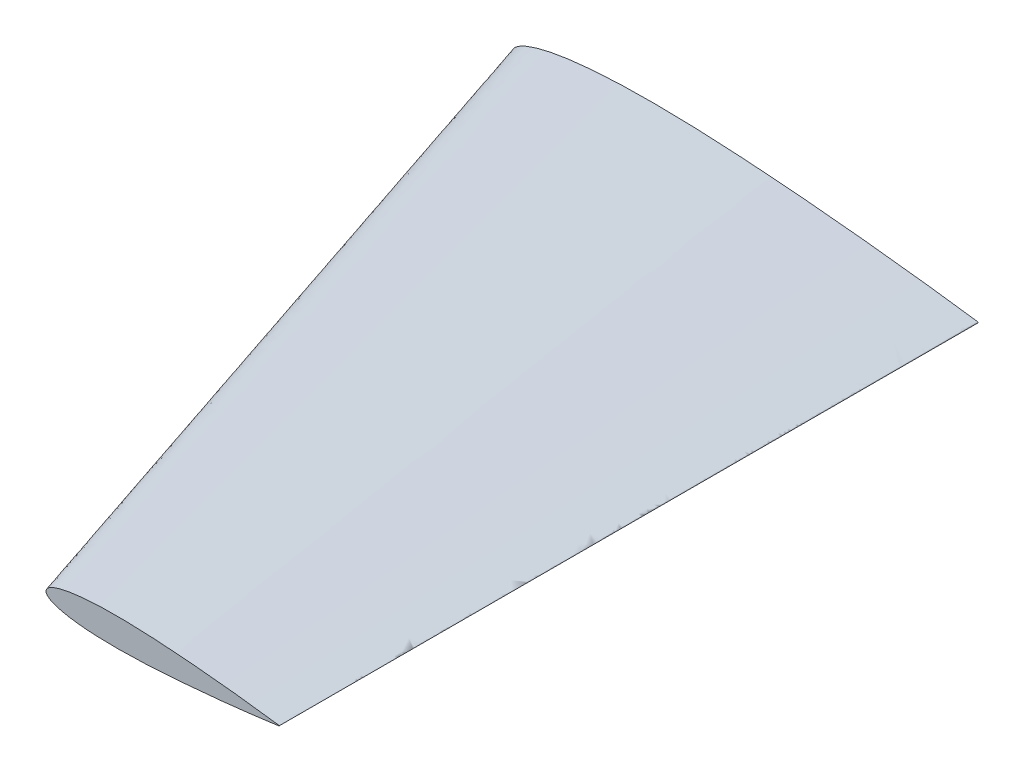
SolidWorks part; units mm, degrees
ref_plane "Front Plane" through (0, 0, 0) normal (1, 0, 0) x (0, 1, 0)
ref_plane "Top Plane" through (0, 0, 0) normal (0, 0, 1) x (0, 1, 0)
ref_plane "Right Plane" through (0, 0, 0) normal (0, 1, 0) x (-1, 0, 0)
curve "Curve2"
  spline degree 3 poles (90, 0.1134, 0) (89.9538, 0.1199, 0) (89.7691, 0.1458, 0) (89.3547, 0.2036, 0) (88.6668, 0.299, 0) (87.7097, 0.43, 0) (86.4894, 0.595, 0) (85.0132, 0.7907, 0) (83.2903, 1.0144, 0) (81.3314, 1.2627, 0) (79.1484, 1.5322, 0) (76.7549, 1.8188, 0) (74.1657, 2.1193, 0) (71.3966, 2.4294, 0) (68.4648, 2.7453, 0) (65.3883, 3.0632, 0) (62.1861, 3.379, 0) (58.878, 3.6881, 0) (55.4843, 3.9866, 0) (52.026, 4.2695, 0) (48.5244, 4.5321, 0) (45.001, 4.7696, 0) (41.4775, 4.977, 0) (37.9757, 5.149, 0) (34.5172, 5.2811, 0) (31.1233, 5.369, 0) (27.8148, 5.4084, 0) (24.6121, 5.3961, 0) (21.5349, 5.3298, 0) (18.6023, 5.2078, 0) (15.8322, 5.0298, 0) (13.2417, 4.7963, 0) (10.8466, 4.5092, 0) (8.6616, 4.1708, 0) (6.6998, 3.7847, 0) (4.9728, 3.3553, 0) (3.4903, 2.8868, 0) (2.26, 2.3835, 0) (1.2857, 1.8489, 0) (0.569, 1.2818, 0) (0.1099, 0.6686, 0) (-0.0512, 0, 0) (0.1099, -0.6686, 0) (0.569, -1.2818, 0) (1.2857, -1.8489, 0) (2.26, -2.3835, 0) (3.4903, -2.8868, 0) (4.9728, -3.3553, 0) (6.6998, -3.7847, 0) (8.6616, -4.1708, 0) (10.8466, -4.5092, 0) (13.2417, -4.7963, 0) (15.8322, -5.0298, 0) (18.6023, -5.2078, 0) (21.5349, -5.3298, 0) (24.6121, -5.3961, 0) (27.8148, -5.4084, 0) (31.1233, -5.369, 0) (34.5172, -5.2811, 0) (37.9757, -5.149, 0) (41.4775, -4.977, 0) (45.001, -4.7696, 0) (48.5244, -4.5321, 0) (52.026, -4.2695, 0) (55.4843, -3.9866, 0) (58.878, -3.6881, 0) (62.1861, -3.379, 0) (65.3883, -3.0632, 0) (68.4648, -2.7453, 0) (71.3966, -2.4294, 0) (74.1657, -2.1193, 0) (76.7549, -1.8188, 0) (79.1484, -1.5322, 0) (81.3314, -1.2627, 0) (83.2903, -1.0144, 0) (85.0132, -0.7907, 0) (86.4894, -0.595, 0) (87.7097, -0.43, 0) (88.6668, -0.299, 0) (89.3547, -0.2036, 0) (89.7691, -0.1458, 0) (89.9538, -0.1199, 0) (90, -0.1134, 0) knots 0 0 0 0 0.000763 0.003048 0.006841 0.012116 0.018841 0.026973 0.03646 0.047243 0.059254 0.072417 0.086651 0.101866 0.117969 0.134858 0.152428 0.170572 0.189175 0.208122 0.227297 0.24658 0.265853 0.284997 0.303895 0.322433 0.340499 0.357984 0.374788 0.390812 0.405965 0.420162 0.433328 0.445394 0.456301 0.466004 0.474472 0.481696 0.487704 0.492583 0.496544 0.5 0.503456 0.507417 0.512296 0.518304 0.525528 0.533996 0.543699 0.554606 0.566672 0.579838 0.594035 0.609188 0.625212 0.642016 0.659501 0.677567 0.696105 0.715003 0.734147 0.75342 0.772703 0.791878 0.810825 0.829428 0.847572 0.865142 0.882031 0.898134 0.913349 0.927583 0.940746 0.952757 0.96354 0.973027 0.981159 0.987884 0.993159 0.996952 0.999237 1 1 1 1
sketch "Sketch2" plane through (0, 0, 0) normal (0, 0, 1) x (0, 1, 0)
  arc A0 (-0.1134, -90) -> (0.1134, -90) centre (0, -89.9841) ccw
  spline S0 degree 3 poles (1966.8421, -449.5678) (-10.9329, -144.6657) (-3.7009, -117.3601) (0.2036, -89.3547) (0.299, -88.6668) (0.43, -87.7097) (0.595, -86.4894) (0.7907, -85.0132) (1.0144, -83.2903) (1.2627, -81.3314) (1.5322, -79.1484) (1.8188, -76.7549) (2.1193, -74.1657) (2.4294, -71.3966) (2.7453, -68.4648) (3.0632, -65.3883) (3.379, -62.1861) (3.6881, -58.878) (3.9866, -55.4843) (4.2695, -52.026) (4.5321, -48.5244) (4.7696, -45.001) (4.977, -41.4775) (5.149, -37.9757) (5.2811, -34.5172) (5.369, -31.1233) (5.4084, -27.8148) (5.3961, -24.6121) (5.3298, -21.5349) (5.2078, -18.6023) (5.0298, -15.8322) (4.7963, -13.2417) (4.5092, -10.8466) (4.1708, -8.6616) (3.7847, -6.6998) (3.3553, -4.9728) (2.8868, -3.4903) (2.3835, -2.26) (1.8489, -1.2857) (1.2818, -0.569) (0.6686, -0.1099) (0, 0.0512) (-0.6686, -0.1099) (-1.2818, -0.569) (-1.8489, -1.2857) (-2.3835, -2.26) (-2.8868, -3.4903) (-3.3553, -4.9728) (-3.7847, -6.6998) (-4.1708, -8.6616) (-4.5092, -10.8466) (-4.7963, -13.2417) (-5.0298, -15.8322) (-5.2078, -18.6023) (-5.3298, -21.5349) (-5.3961, -24.6121) (-5.4084, -27.8148) (-5.369, -31.1233) (-5.2811, -34.5172) (-5.149, -37.9757) (-4.977, -41.4775) (-4.7696, -45.001) (-4.5321, -48.5244) (-4.2695, -52.026) (-3.9866, -55.4843) (-3.6881, -58.878) (-3.379, -62.1861) (-3.0632, -65.3883) (-2.7453, -68.4648) (-2.4294, -71.3966) (-2.1193, -74.1657) (-1.8188, -76.7549) (-1.5322, -79.1484) (-1.2627, -81.3314) (-1.0144, -83.2903) (-0.7907, -85.0132) (-0.595, -86.4894) (-0.43, -87.7097) (-0.299, -88.6668) (-0.2036, -89.3547) (3.7009, -117.36) (10.9329, -144.6654) (-1966.8144, -449.5636) knots -0.45542 -0.45542 -0.45542 -0.45542 0.000763 0.003048 0.006841 0.012116 0.018841 0.026973 0.03646 0.047243 0.059254 0.072417 0.086651 0.101866 0.117969 0.134858 0.152428 0.170572 0.189175 0.208122 0.227297 0.24658 0.265853 0.284997 0.303895 0.322433 0.340499 0.357984 0.374788 0.390812 0.405965 0.420162 0.433328 0.445394 0.456301 0.466004 0.474472 0.481696 0.487704 0.492583 0.496544 0.5 0.503456 0.507417 0.512296 0.518304 0.525528 0.533996 0.543699 0.554606 0.566672 0.579838 0.594035 0.609188 0.625212 0.642016 0.659501 0.677567 0.696105 0.715003 0.734147 0.75342 0.772703 0.791878 0.810825 0.829428 0.847572 0.865142 0.882031 0.898134 0.913349 0.927583 0.940746 0.952757 0.96354 0.973027 0.981159 0.987884 0.993159 0.996952 0.999237 1.455418 1.455418 1.455418 1.455418 only from (0.1134, -90) to (-0.1134, -90) construction
  spline S1 degree 3 poles (0.1134, -90) (0.1199, -89.9538) (0.1458, -89.7691) (0.2036, -89.3547) (0.299, -88.6668) (0.43, -87.7097) (0.595, -86.4894) (0.7907, -85.0132) (1.0144, -83.2903) (1.2627, -81.3314) (1.5322, -79.1484) (1.8188, -76.7549) (2.1193, -74.1657) (2.4294, -71.3966) (2.7453, -68.4648) (3.0632, -65.3883) (3.379, -62.1861) (3.6881, -58.878) (3.9866, -55.4843) (4.2695, -52.026) (4.5321, -48.5244) (4.7696, -45.001) (4.977, -41.4775) (5.149, -37.9757) (5.2811, -34.5172) (5.369, -31.1233) (5.4084, -27.8148) (5.3961, -24.6121) (5.3298, -21.5349) (5.2078, -18.6023) (5.0298, -15.8322) (4.7963, -13.2417) (4.5092, -10.8466) (4.1708, -8.6616) (3.7847, -6.6998) (3.3553, -4.9728) (2.8868, -3.4903) (2.3835, -2.26) (1.8489, -1.2857) (1.2818, -0.569) (0.6686, -0.1099) (0, 0.0512) (-0.6686, -0.1099) (-1.2818, -0.569) (-1.8489, -1.2857) (-2.3835, -2.26) (-2.8868, -3.4903) (-3.3553, -4.9728) (-3.7847, -6.6998) (-4.1708, -8.6616) (-4.5092, -10.8466) (-4.7963, -13.2417) (-5.0298, -15.8322) (-5.2078, -18.6023) (-5.3298, -21.5349) (-5.3961, -24.6121) (-5.4084, -27.8148) (-5.369, -31.1233) (-5.2811, -34.5172) (-5.149, -37.9757) (-4.977, -41.4775) (-4.7696, -45.001) (-4.5321, -48.5244) (-4.2695, -52.026) (-3.9866, -55.4843) (-3.6881, -58.878) (-3.379, -62.1861) (-3.0632, -65.3883) (-2.7453, -68.4648) (-2.4294, -71.3966) (-2.1193, -74.1657) (-1.8188, -76.7549) (-1.5322, -79.1484) (-1.2627, -81.3314) (-1.0144, -83.2903) (-0.7907, -85.0132) (-0.595, -86.4894) (-0.43, -87.7097) (-0.299, -88.6668) (-0.2036, -89.3547) (-0.1458, -89.7691) (-0.1199, -89.9538) (-0.1134, -90) knots 0 0 0 0 0.000763 0.003048 0.006841 0.012116 0.018841 0.026973 0.03646 0.047243 0.059254 0.072417 0.086651 0.101866 0.117969 0.134858 0.152428 0.170572 0.189175 0.208122 0.227297 0.24658 0.265853 0.284997 0.303895 0.322433 0.340499 0.357984 0.374788 0.390812 0.405965 0.420162 0.433328 0.445394 0.456301 0.466004 0.474472 0.481696 0.487704 0.492583 0.496544 0.5 0.503456 0.507417 0.512296 0.518304 0.525528 0.533996 0.543699 0.554606 0.566672 0.579838 0.594035 0.609188 0.625212 0.642016 0.659501 0.677567 0.696105 0.715003 0.734147 0.75342 0.772703 0.791878 0.810825 0.829428 0.847572 0.865142 0.882031 0.898134 0.913349 0.927583 0.940746 0.952757 0.96354 0.973027 0.981159 0.987884 0.993159 0.996952 0.999237 1 1 1 1
curve "Curve3"
  spline degree 3 poles (45, 0.0567, 0) (44.9912, 0.0579, 0) (44.9562, 0.0628, 0) (44.8775, 0.0739, 0) (44.7466, 0.0922, 0) (44.5636, 0.1176, 0) (44.3292, 0.15, 0) (44.0438, 0.1892, 0) (43.708, 0.2349, 0) (43.3227, 0.2868, 0) (42.8888, 0.3447, 0) (42.4073, 0.4081, 0) (41.8793, 0.4768, 0) (41.306, 0.5503, 0) (40.6888, 0.6281, 0) (40.0291, 0.71, 0) (39.3285, 0.7954, 0) (38.5885, 0.884, 0) (37.811, 0.9753, 0) (36.9978, 1.0688, 0) (36.1506, 1.1641, 0) (35.2716, 1.2607, 0) (34.3628, 1.3582, 0) (33.4263, 1.4561, 0) (32.4642, 1.554, 0) (31.4789, 1.6513, 0) (30.4726, 1.7476, 0) (29.4476, 1.8424, 0) (28.4065, 1.935, 0) (27.3515, 2.0251, 0) (26.2853, 2.112, 0) (25.2101, 2.1952, 0) (24.1287, 2.2742, 0) (23.0434, 2.3482, 0) (21.9569, 2.4169, 0) (20.8717, 2.4795, 0) (19.7902, 2.5354, 0) (18.7151, 2.5842, 0) (17.6488, 2.6253, 0) (16.5938, 2.6582, 0) (15.5526, 2.6822, 0) (14.5276, 2.6971, 0) (13.5213, 2.7024, 0) (12.5359, 2.6978, 0) (11.5738, 2.6829, 0) (10.6371, 2.6576, 0) (9.7282, 2.6217, 0) (8.8491, 2.5751, 0) (8.0019, 2.5179, 0) (7.1884, 2.45, 0) (6.4108, 2.3718, 0) (5.6707, 2.2834, 0) (4.9698, 2.1851, 0) (4.3099, 2.0772, 0) (3.6923, 1.9603, 0) (3.1187, 1.8346, 0) (2.5902, 1.7008, 0) (2.108, 1.5593, 0) (1.6732, 1.4107, 0) (1.2869, 1.2554, 0) (0.9496, 1.0939, 0) (0.662, 0.9266, 0) (0.4245, 0.7537, 0) (0.2376, 0.5749, 0) (0.1017, 0.3898, 0) (0.0185, 0.1974, 0) (-0.009, 0, 0) (0.0185, -0.1974, 0) (0.1017, -0.3898, 0) (0.2376, -0.5749, 0) (0.4245, -0.7537, 0) (0.662, -0.9266, 0) (0.9496, -1.0939, 0) (1.2869, -1.2554, 0) (1.6732, -1.4107, 0) (2.108, -1.5593, 0) (2.5902, -1.7008, 0) (3.1187, -1.8346, 0) (3.6923, -1.9603, 0) (4.3099, -2.0772, 0) (4.9698, -2.1851, 0) (5.6707, -2.2834, 0) (6.4108, -2.3718, 0) (7.1884, -2.45, 0) (8.0019, -2.5179, 0) (8.8491, -2.5751, 0) (9.7282, -2.6217, 0) (10.6371, -2.6576, 0) (11.5738, -2.6829, 0) (12.5359, -2.6978, 0) (13.5213, -2.7024, 0) (14.5276, -2.6971, 0) (15.5526, -2.6822, 0) (16.5938, -2.6582, 0) (17.6488, -2.6253, 0) (18.7151, -2.5842, 0) (19.7902, -2.5354, 0) (20.8717, -2.4795, 0) (21.9569, -2.4169, 0) (23.0434, -2.3482, 0) (24.1287, -2.2742, 0) (25.2101, -2.1952, 0) (26.2853, -2.112, 0) (27.3515, -2.0251, 0) (28.4065, -1.935, 0) (29.4476, -1.8424, 0) (30.4726, -1.7476, 0) (31.4789, -1.6513, 0) (32.4642, -1.554, 0) (33.4263, -1.4561, 0) (34.3628, -1.3582, 0) (35.2716, -1.2607, 0) (36.1506, -1.1641, 0) (36.9978, -1.0688, 0) (37.811, -0.9753, 0) (38.5885, -0.884, 0) (39.3285, -0.7954, 0) (40.0291, -0.71, 0) (40.6888, -0.6281, 0) (41.306, -0.5503, 0) (41.8793, -0.4768, 0) (42.4073, -0.4081, 0) (42.8888, -0.3447, 0) (43.3227, -0.2868, 0) (43.708, -0.2349, 0) (44.0438, -0.1892, 0) (44.3292, -0.15, 0) (44.5636, -0.1176, 0) (44.7466, -0.0922, 0) (44.8775, -0.0739, 0) (44.9562, -0.0628, 0) (44.9912, -0.0579, 0) (45, -0.0567, 0) knots 0 0 0 0 0.000289 0.001156 0.002598 0.004612 0.007194 0.010336 0.014031 0.018271 0.023046 0.028343 0.03415 0.040454 0.047239 0.054489 0.062186 0.070314 0.078852 0.08778 0.097077 0.106722 0.116691 0.126961 0.137507 0.148306 0.159331 0.170557 0.181957 0.193504 0.205172 0.216932 0.228758 0.240621 0.252495 0.26435 0.276161 0.287898 0.299536 0.311047 0.322405 0.333584 0.344559 0.355306 0.3658 0.376018 0.385938 0.395538 0.404798 0.413699 0.422222 0.430349 0.438066 0.445357 0.452209 0.458611 0.464554 0.47003 0.475035 0.479569 0.483637 0.48725 0.490431 0.493219 0.495674 0.497891 0.5 0.502109 0.504326 0.506781 0.509569 0.51275 0.516363 0.520431 0.524965 0.52997 0.535446 0.541389 0.547791 0.554643 0.561934 0.569651 0.577778 0.586301 0.595202 0.604462 0.614062 0.623982 0.6342 0.644694 0.655441 0.666416 0.677595 0.688953 0.700464 0.712102 0.723839 0.73565 0.747505 0.759379 0.771242 0.783068 0.794828 0.806496 0.818043 0.829443 0.840669 0.851694 0.862493 0.873039 0.883309 0.893278 0.902923 0.91222 0.921148 0.929686 0.937814 0.945511 0.952761 0.959546 0.96585 0.971657 0.976954 0.981729 0.985969 0.989664 0.992806 0.995388 0.997402 0.998844 0.999711 1 1 1 1
ref_plane "Plane1" through (0, 0, 135) normal (0, 0, 1) x (0, 1, 0)
sketch "Sketch3" plane through (0, 0, 135) normal (0, 0, 1) x (0, 1, 0)
  arc A5 (-0.0567, -89.992) -> (0.0567, -89.992) centre (0, -89.9841) ccw
  spline S3 degree 3 poles (0.0567, -89.992) (0.0579, -89.9833) (0.0628, -89.9483) (0.0739, -89.8696) (0.1164, -89.5652) (0.1702, -89.1751) (0.2349, -88.7) (0.2868, -88.3148) (0.3447, -87.8809) (0.4081, -87.3993) (0.4768, -86.8713) (0.5503, -86.298) (0.6281, -85.6808) (0.71, -85.0211) (0.8601, -83.7902) (1.0118, -82.4964) (1.1641, -81.1427) (1.295, -79.9514) (1.4253, -78.7216) (1.5881, -77.1207) (1.751, -75.4464) (1.9058, -73.7406) (2.0557, -71.9851) (2.1692, -70.5581) (2.2742, -69.1207) (2.3482, -68.0355) (2.4169, -66.9489) (2.4795, -65.8637) (2.5354, -64.7822) (2.5842, -63.7071) (2.6253, -62.6408) (2.6582, -61.5858) (2.6822, -60.5446) (2.6971, -59.5197) (2.7024, -58.5133) (2.6978, -57.5279) (2.6829, -56.5658) (2.6576, -55.6292) (2.6217, -54.7202) (2.5751, -53.8411) (2.5179, -52.9939) (2.45, -52.1805) (2.3718, -51.4028) (2.2834, -50.6627) (2.1851, -49.9618) (2.0772, -49.3019) (1.9603, -48.6844) (1.8346, -48.1107) (1.7008, -47.5822) (1.5593, -47.1) (1.4107, -46.6653) (1.2554, -46.2789) (1.0939, -45.9416) (0.9266, -45.654) (0.7537, -45.4166) (0.5749, -45.2296) (0.3898, -45.0937) (0.1974, -45.0106) (0, -44.983) (-0.1974, -45.0106) (-0.3898, -45.0937) (-0.5749, -45.2296) (-0.7537, -45.4166) (-0.9266, -45.654) (-1.0939, -45.9416) (-1.2554, -46.2789) (-1.4107, -46.6653) (-1.5593, -47.1) (-1.7008, -47.5822) (-1.8346, -48.1107) (-1.9603, -48.6844) (-2.0772, -49.3019) (-2.1851, -49.9618) (-2.2834, -50.6627) (-2.3718, -51.4028) (-2.45, -52.1805) (-2.5179, -52.9939) (-2.5751, -53.8411) (-2.6217, -54.7202) (-2.6576, -55.6292) (-2.6829, -56.5658) (-2.6978, -57.5279) (-2.7024, -58.5133) (-2.6971, -59.5197) (-2.6822, -60.5446) (-2.6582, -61.5858) (-2.6253, -62.6408) (-2.5842, -63.7071) (-2.5354, -64.7822) (-2.4795, -65.8637) (-2.4169, -66.9489) (-2.3482, -68.0355) (-2.2742, -69.1207) (-2.1692, -70.5581) (-2.0557, -71.9851) (-1.9058, -73.7406) (-1.751, -75.4464) (-1.5577, -77.4334) (-1.3926, -79.0341) (-1.2607, -80.2637) (-1.1641, -81.1427) (-1.0396, -82.2493) (-0.9165, -83.3094) (-0.7954, -84.3205) (-0.71, -85.0211) (-0.6281, -85.6808) (-0.5503, -86.298) (-0.4768, -86.8713) (-0.4081, -87.3993) (-0.3447, -87.8809) (-0.2868, -88.3148) (-0.2115, -88.8735) (-0.1464, -89.3485) (-0.0922, -89.7386) (-0.0739, -89.8696) (-0.0628, -89.9483) (-0.0579, -89.9833) (-0.0567, -89.992) knots 0 0 0 0 0.000289 0.001156 0.002598 0.010336 0.014031 0.018271 0.023046 0.028343 0.03415 0.040454 0.047239 0.054489 0.062186 0.08778 0.097077 0.106722 0.126961 0.137507 0.159331 0.181957 0.193504 0.216932 0.228758 0.240621 0.252495 0.26435 0.276161 0.287898 0.299536 0.311047 0.322405 0.333584 0.344559 0.355306 0.3658 0.376018 0.385938 0.395538 0.404798 0.413699 0.422222 0.430349 0.438066 0.445357 0.452209 0.458611 0.464554 0.47003 0.475035 0.479569 0.483637 0.48725 0.490431 0.493219 0.495674 0.497891 0.5 0.502109 0.504326 0.506781 0.509569 0.51275 0.516363 0.520431 0.524965 0.52997 0.535446 0.541389 0.547791 0.554643 0.561934 0.569651 0.577778 0.586301 0.595202 0.604462 0.614062 0.623982 0.6342 0.644694 0.655441 0.666416 0.677595 0.688953 0.700464 0.712102 0.723839 0.73565 0.747505 0.759379 0.771242 0.783068 0.806496 0.818043 0.840669 0.862493 0.883309 0.893278 0.902923 0.91222 0.929686 0.937814 0.945511 0.952761 0.959546 0.96585 0.971657 0.976954 0.981729 0.985969 0.995388 0.997402 0.998844 0.999711 1 1 1 1
loft "Loft3" add profiles "Sketch2", "Sketch3" connector at (90, -0.1134, 0) connector at (89.992, -0.0567, 135)
sketch "Sketch4" plane through (0, 0, 0) normal (0, 0, -1) x (1, 0, 0)
  circle A0 centre (39.9841, 0) radius 3.175
  arc A3 (90, -0.1134) -> (90, 0.1134) centre (89.9841, 0) ccw
  arc A4 (90, -0.1134) -> (90, 0.1134) centre (89.9841, 0) ccw
  spline S4 degree 3 poles (2097.8875, -2141.6804) (81.2904, 65.0706) (-6.184, 7.7379) (0.5688, -1.2818) (1.2856, -1.8489) (2.2599, -2.3835) (3.4902, -2.8868) (4.9726, -3.3553) (6.6996, -3.7847) (8.6614, -4.1708) (10.8465, -4.5092) (13.2416, -4.7963) (15.8321, -5.0298) (18.6022, -5.2079) (21.5348, -5.3299) (24.6119, -5.3961) (27.8146, -5.4084) (31.1231, -5.369) (34.5171, -5.2811) (37.9756, -5.149) (41.4774, -4.977) (45.0009, -4.7696) (48.5243, -4.5321) (52.026, -4.2695) (55.4843, -3.9866) (58.878, -3.6881) (62.1861, -3.379) (65.3883, -3.0632) (68.4648, -2.7453) (71.3966, -2.4294) (74.1657, -2.1193) (76.7549, -1.8188) (79.1484, -1.5322) (81.3313, -1.2627) (83.2903, -1.0144) (85.0132, -0.7907) (86.4894, -0.595) (87.7097, -0.43) (88.6668, -0.299) (89.3547, -0.2036) (121.3566, 4.2581) (152.5138, 13.0837) (600.1044, -2955.3731) knots -0.168575 -0.168575 -0.168575 -0.168575 0.003456 0.007417 0.012296 0.018304 0.025528 0.033996 0.043699 0.054606 0.066672 0.079838 0.094035 0.109188 0.125212 0.142016 0.159501 0.177567 0.196105 0.215003 0.234147 0.25342 0.272703 0.291878 0.310825 0.329428 0.347572 0.365142 0.382031 0.398134 0.413349 0.427583 0.440746 0.452757 0.46354 0.473027 0.481159 0.487884 0.493159 0.496952 0.499237 1.021387 1.021387 1.021387 1.021387 only from (-0.0002, 0) to (90, -0.1134)
  spline S5 degree 3 poles (260.8421, -2934.404) (598.8583, -252.7331) (351.7953, -32.5821) (78.6263, 1.6023) (72.9292, 2.2653) (67.2268, 2.8806) (62.4707, 3.3538) (58.6634, 3.7067) (55.8067, 3.9581) (52.9488, 4.195) (50.0896, 4.4164) (47.2292, 4.6211) (44.3675, 4.8074) (41.5046, 4.9736) (38.6405, 5.1171) (35.7752, 5.2356) (32.9088, 5.3262) (30.0417, 5.3852) (27.174, 5.4083) (24.3062, 5.3906) (21.917, 5.3367) (20.0065, 5.2661) (18.5742, 5.1983) (17.1428, 5.1142) (15.7125, 5.0123) (14.2838, 4.8906) (12.8571, 4.7469) (11.4331, 4.5785) (10.0127, 4.3816) (8.5973, 4.1517) (7.4235, 3.9274) (6.4895, 3.7238) (5.7921, 3.5576) (5.0986, 3.3755) (4.41, 3.1758) (3.7279, 2.9545) (3.0547, 2.7077) (2.3937, 2.429) (1.7518, 2.1091) (1.1389, 1.7346) (0.5816, 1.2805) (-6.4398, -7.5194) (75.7669, -67.508) (2215.6517, 2017.9535) knots -3.89743 -3.89743 -3.89743 -3.89743 0.532086 0.56328 0.594474 0.625669 0.656863 0.67246 0.688057 0.703654 0.719251 0.734849 0.750446 0.766043 0.78164 0.797237 0.812834 0.828431 0.844029 0.859626 0.875223 0.883021 0.89082 0.898619 0.906417 0.914216 0.922014 0.929813 0.937611 0.94541 0.953209 0.957108 0.961007 0.964906 0.968806 0.972705 0.976604 0.980504 0.984403 0.988302 0.992201 0.996101 1.170104 1.170104 1.170104 1.170104 only from (90, 0.1134) to (-0.0002, 0)
  spline S6 degree 3 poles (-0.0002, 0) (-0.0002, -0.2126) (0.1097, -0.6686) (0.5688, -1.2818) (1.2856, -1.8489) (2.2599, -2.3835) (3.4902, -2.8868) (4.9726, -3.3553) (6.6996, -3.7847) (8.6614, -4.1708) (10.8465, -4.5092) (13.2416, -4.7963) (15.8321, -5.0298) (18.6022, -5.2079) (21.5348, -5.3299) (24.6119, -5.3961) (27.8146, -5.4084) (31.1231, -5.369) (34.5171, -5.2811) (37.9756, -5.149) (41.4774, -4.977) (45.0009, -4.7696) (48.5243, -4.5321) (52.026, -4.2695) (55.4843, -3.9866) (58.878, -3.6881) (62.1861, -3.379) (65.3883, -3.0632) (68.4648, -2.7453) (71.3966, -2.4294) (74.1657, -2.1193) (76.7549, -1.8188) (79.1484, -1.5322) (81.3313, -1.2627) (83.2903, -1.0144) (85.0132, -0.7907) (86.4894, -0.595) (87.7097, -0.43) (88.6668, -0.299) (89.3547, -0.2036) (89.7691, -0.1458) (89.9538, -0.1199) (90, -0.1134) knots 0 0 0 0 0.003456 0.007417 0.012296 0.018304 0.025528 0.033996 0.043699 0.054606 0.066672 0.079838 0.094035 0.109188 0.125212 0.142016 0.159501 0.177567 0.196105 0.215003 0.234147 0.25342 0.272703 0.291878 0.310825 0.329428 0.347572 0.365142 0.382031 0.398134 0.413349 0.427583 0.440746 0.452757 0.46354 0.473027 0.481159 0.487884 0.493159 0.496952 0.499237 0.5 0.5 0.5 0.5
  spline S7 degree 3 poles (90, 0.1134) (88.1067, 0.3789) (84.3174, 0.8901) (78.6263, 1.6023) (72.9292, 2.2653) (67.2268, 2.8806) (62.4707, 3.3538) (58.6634, 3.7067) (55.8067, 3.9581) (52.9488, 4.195) (50.0896, 4.4164) (47.2292, 4.6211) (44.3675, 4.8074) (41.5046, 4.9736) (38.6405, 5.1171) (35.7752, 5.2356) (32.9088, 5.3262) (30.0417, 5.3852) (27.174, 5.4083) (24.3062, 5.3906) (21.917, 5.3367) (20.0065, 5.2661) (18.5742, 5.1983) (17.1428, 5.1142) (15.7125, 5.0123) (14.2838, 4.8906) (12.8571, 4.7469) (11.4331, 4.5785) (10.0127, 4.3816) (8.5973, 4.1517) (7.4235, 3.9274) (6.4895, 3.7238) (5.7921, 3.5576) (5.0986, 3.3755) (4.41, 3.1758) (3.7279, 2.9545) (3.0547, 2.7077) (2.3937, 2.429) (1.7518, 2.1091) (1.1389, 1.7346) (0.5816, 1.2805) (0.1299, 0.7143) (-0.0002, 0.2381) (-0.0002, 0) knots 0.500891 0.500891 0.500891 0.500891 0.532086 0.56328 0.594474 0.625669 0.656863 0.67246 0.688057 0.703654 0.719251 0.734849 0.750446 0.766043 0.78164 0.797237 0.812834 0.828431 0.844029 0.859626 0.875223 0.883021 0.89082 0.898619 0.906417 0.914216 0.922014 0.929813 0.937611 0.94541 0.953209 0.957108 0.961007 0.964906 0.968806 0.972705 0.976604 0.980504 0.984403 0.988302 0.992201 0.996101 1 1 1 1
  dimension "D2" = 6.35
  dimension "D3" = 50
  dimension "D1" = 0
extrude "Cut-Extrude3" cut sketch "Sketch4" against normal blind 40 contours A0 region at (39.9841, 0, 0)
